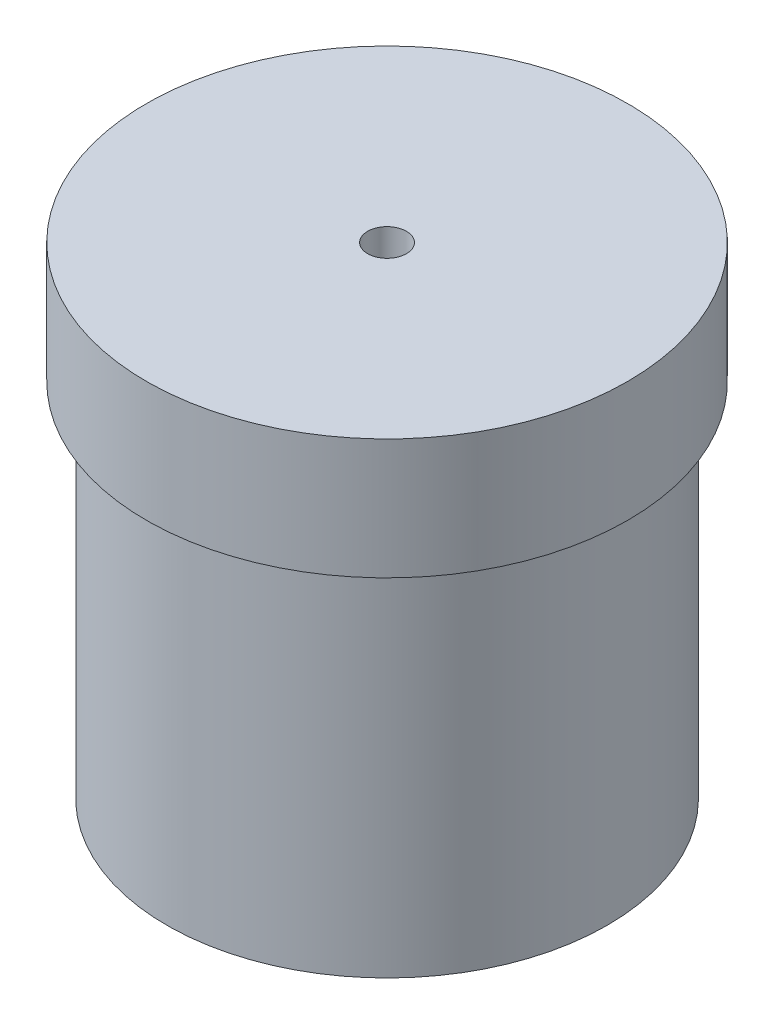
SolidWorks part; units mm, degrees
ref_plane "Front Plane" through (0, 0, 0) normal (0, 0, 1) x (1, 0, 0)
ref_plane "Top Plane" through (0, 0, 0) normal (0, 1, 0) x (1, 0, 0)
ref_plane "Right Plane" through (0, 0, 0) normal (1, 0, 0) x (0, 0, -1)
sketch "Sketch1" plane through (0, 0, 0) normal (0, 0, 1) x (1, 0, 0)
  line L0 (0, 12.7) -> (-12.7, 12.7)
  line L1 (-12.7, 12.7) -> (-12.7, 6.35)
  line L2 (-12.7, 6.35) -> (-11.6205, 6.35)
  line L3 (-11.6205, 6.35) -> (-11.6205, -12.7)
  line L4 (-11.6205, -12.7) -> (0, -12.7)
  line L5 (0, -12.7) -> (0, 12.7) construction
  line L6 (0, 12.7) -> (0, -12.7)
  point P4 (0, 0)
  point P7 (-23.241, 6.35)
  point P9 (-28.4296, 7.1193)
  dimension "D1" = 11.6205
  dimension "D2" = 12.7
  dimension "D3" = 6.35
  dimension "D4" = 25.4
revolve "Revolve1" add sketch "Sketch1" angle 360 about L5
hole_wizard "M2.5x0.45 Tapped Hole1" positions "Sketch2" profile "Sketch3" tap size "M2.5x0.45" standard "ANSI Metric"
sketch "Sketch2" plane through (0, 12.7, 0) normal (0, 1, 0) x (1, 0, 0)
  point P0 (0, 0)
sketch "Sketch3" plane through (0, 12.7, 0) normal (1, 0, 0) x (0, 0, 1)
  line L0 (0, 0) -> (0, 6.9659)
  line L1 (0, 6.9659) -> (1.025, 6.35)
  line L2 (1.025, 6.35) -> (1.025, 0)
  line L5 (1.025, 0) -> (0, 0)
  line L10 (0, 6.9659) -> (-1.025, 6.35) construction
  line L11 (0, -6.35) -> (0, 107.95) construction
  dimension "Tap Drill Dia." = 2.05
  dimension "Tap Drill Depth" = 6.35
  dimension "Drill Angle" = 118
cosmetic thread "Hole Thread1" parameters "D1"=5.08, "D2"=2.5
